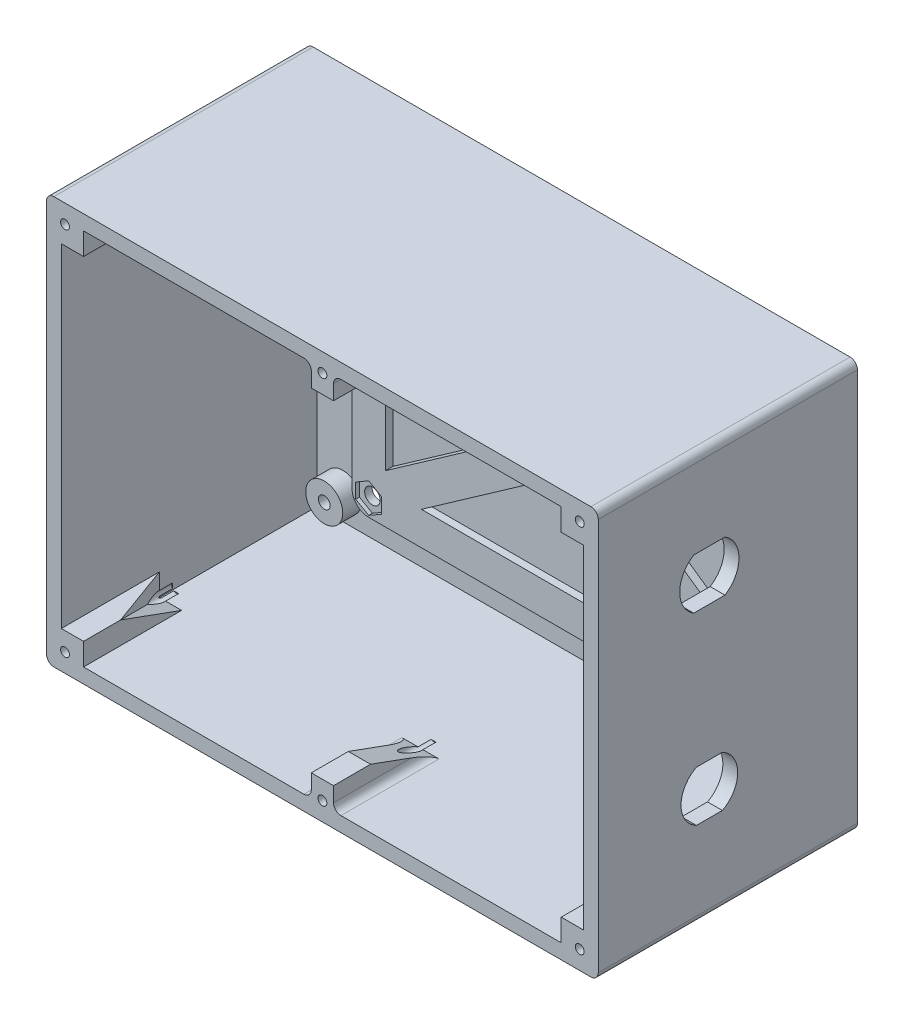
SolidWorks part; units mm, degrees
ref_plane "Přední rovina" through (0, 0, 0) normal (0, 0, 1) x (1, 0, 0)
ref_plane "Horní rovina" through (0, 0, 0) normal (0, 1, 0) x (1, 0, 0)
ref_plane "Pravá rovina" through (0, 0, 0) normal (1, 0, 0) x (0, 0, -1)
sketch "Skica1" plane through (0, 0, 0) normal (0, 0, 1) x (1, 0, 0)
  line L1 (-50, -50) -> (50, -50) construction
  line L2 (-50, -50) -> (-50, 50) construction
  line L3 (-50, 50) -> (50, 50) construction
  line L4 (50, -50) -> (50, 50) construction
  line L5 (-50, -50) -> (50, 50) construction
  line L6 (-50, 50) -> (50, -50) construction
  line L7 (-51, -51) -> (90, -51)
  line L8 (-51, -51) -> (-51, 51)
  line L9 (-51, 51) -> (90, 51)
  line L10 (90, -51) -> (90, 51)
  line L11 (-55, -55) -> (94, -55)
  line L12 (-55, -55) -> (-55, 55)
  line L13 (-55, 55) -> (94, 55)
  line L14 (94, -55) -> (94, 55)
  point P0 (0, 0)
  dimension "D1" = 100
  dimension "D2" = 2
  dimension "D3" = 2
  dimension "D4" = 2
  dimension "D5" = 40
  dimension "D6" = 4
  dimension "D7" = 4
  dimension "D8" = 4
  dimension "D9" = 4
extrude "Přidat vysunutím1" add sketch "Skica1" along normal blind 70
extrude "Přidat vysunutím2" add sketch "Skica1<3>" along normal blind 1 contours L7 L10 L9 L8 region at (19.5, 0, 0)
sketch "Skica1<3>" plane through (0, 0, 0) normal (0, 0, 1) x (1, 0, 0) same geometry as "Skica1"
sketch "Skica2" plane through (0, 0, 1) normal (0, 0, 1) x (1, 0, 0)
  line L0 (90, 51) -> (-51, 51) construction
  line L1 (-49, -49) -> (49, -49) construction
  line L2 (-49, -49) -> (-49, 49) construction
  line L3 (-49, 49) -> (49, 49) construction
  line L20 (49, -49) -> (49, 49) construction
  line L21 (-49, -49) -> (49, 49) construction
  line L22 (-49, 49) -> (49, -49) construction
  line L24 (-44, -44) -> (44, -44) construction
  line L25 (-44, -44) -> (-44, 44) construction
  line L26 (-44, 44) -> (44, 44) construction
  line L27 (44, -44) -> (44, 44) construction
  line L28 (-44, -44) -> (44, 44) construction
  line L29 (-44, 44) -> (44, -44) construction
  circle A0 centre (-44, 44) radius 1.6
  circle A1 centre (44, 44) radius 1.6
  circle A2 centre (44, -44) radius 1.6
  circle A3 centre (-44, -44) radius 1.6
  circle A4 centre (-44, 44) radius 5
  circle A5 centre (44, 44) radius 5
  circle A6 centre (44, -44) radius 5
  circle A7 centre (-44, -44) radius 5
  point P0 (0, 0)
  point P7 (0, 0)
  dimension "D3" = 3.2
  dimension "D1" = 2
  dimension "D2" = 5
extrude "Přidat vysunutím3" add sketch "Skica2" along normal blind 5
extrude "Odebrat vysunutím1" cut sketch "Skica2<2>" against normal through all both and the other way through all contours A0 | A1 | A2 | A3 region at (-44, 44, 1) region at (44, 44, 1) region at (44, -44, 1) region at (-44, -44, 1)
sketch "Skica2<2>" plane through (0, 0, 1) normal (0, 0, 1) x (1, 0, 0) same geometry as "Skica2"
sketch "Skica6" plane through (94, 0, 0) normal (1, 0, 0) x (0, 0, -1)
  line L0 (-40, -55) -> (-40, 55) construction
  line L1 (-70, -55) -> (0, -55) construction
  line L2 (-70, 55) -> (0, 55) construction
  line L3 (-44.2143, 31.8) -> (-35.7857, 31.8)
  line L4 (-44.2143, 18.2) -> (-35.7857, 18.2)
  line L6 (0, -55) -> (0, 55) construction
  line L7 (-43.5046, -18.2) -> (-36.4954, -18.2)
  line L8 (-43.5046, -31.8) -> (-36.4954, -31.8)
  arc A0 (-43.5046, -18.2) -> (-43.5046, -31.8) centre (-40, -25) ccw
  arc A1 (-44.2143, 31.8) -> (-44.2143, 18.2) centre (-40, 25) ccw
  arc A2 (-35.7857, 18.2) -> (-35.7857, 31.8) centre (-40, 25) ccw
  arc A3 (-36.4954, -31.8) -> (-36.4954, -18.2) centre (-40, -25) ccw
  dimension "D1" = 15.3
  dimension "D2" = 16
  dimension "D3" = 13.6
  dimension "D4" = 30
  dimension "D5" = 30
  dimension "D6" = 40
  dimension "D7" = 13.6
extrude "Odebrat vysunutím2" cut sketch "Skica6" against normal up to surface (4 mm away) up to face at (90, 0, 35.5)
sketch "Skica7" plane through (0, 0, 1) normal (0, 0, 1) x (1, 0, 0)
  line L0 (94, 55) -> (-55, 55) construction
  line L1 (-35, -40) -> (79, -40) construction
  line L2 (-35, -40) -> (-35, -37.9) construction
  line L3 (-35, 40) -> (-32.9, 40) construction
  line L4 (79, -40) -> (79, 35.5) construction
  line L5 (-55, -55) -> (94, -55) construction
  line L6 (-55, 55) -> (-55, -55) construction
  line L7 (94, -55) -> (94, 55) construction
  line L8 (76.9, 40) -> (79, 40) construction
  line L9 (74.5, -31.3446) -> (29.8339, 0)
  line L10 (64.7536, 35.5) -> (22, 5.4975)
  line L11 (-20.7536, -35.5) -> (22, -5.4975)
  line L12 (-39.5, 40) -> (-39.5, -40)
  line L13 (-30.5, -31.3446) -> (-30.5, 31.3446)
  line L14 (-35, -44.5) -> (39.0251, -44.5)
  line L15 (64.7536, -35.5) -> (-20.7536, -35.5)
  line L16 (83.5, -40) -> (83.5, 40)
  line L17 (22, -5.4975) -> (64.7536, -35.5)
  line L18 (22, 5.4975) -> (-20.7536, 35.5)
  line L19 (39.0251, 44.5) -> (-35, 44.5)
  line L20 (79, 44.5) -> (48.9749, 44.5)
  line L21 (74.5, 31.3446) -> (74.5, -31.3446)
  line L22 (29.8339, 0) -> (74.5, 31.3446)
  line L23 (14.1661, 0) -> (-30.5, -31.3446)
  line L24 (-30.5, 31.3446) -> (14.1661, 0)
  line L25 (48.9749, -44.5) -> (79, -44.5)
  line L26 (-35, -35.5) -> (-35, 35.5) construction
  line L27 (79, 37.9) -> (79, 40) construction
  line L28 (-20.7536, 35.5) -> (64.7536, 35.5)
  line L30 (71.1661, 40) -> (74.5, 40) construction
  line L31 (-35, 37.9) -> (-35, 40) construction
  circle A0 centre (-35, 40) radius 2.1
  arc A1 (-35, 44.5) -> (-39.5, 40) centre (-35, 40) ccw
  circle A2 centre (79, 40) radius 2.1
  arc A3 (83.5, 40) -> (79, 44.5) centre (79, 40) ccw
  circle A4 centre (79, -40) radius 2.1
  arc A5 (79, -44.5) -> (83.5, -40) centre (79, -40) ccw
  circle A6 centre (-35, -40) radius 2.1
  arc A7 (-39.5, -40) -> (-35, -44.5) centre (-35, -40) ccw
  circle A8 centre (44, 44) radius 5 construction
  circle A9 centre (44, -44) radius 5 construction
  arc A10 (39.0251, 44.5) -> (48.9749, 44.5) centre (44, 44) ccw
  arc A11 (48.9749, -44.5) -> (39.0251, -44.5) centre (44, -44) ccw
  dimension "D5" = 4.2
  dimension "D6" = 9
  dimension "D1" = 15
  dimension "D2" = 15
  dimension "D3" = 20
  dimension "D4" = 15
extrude "Přidat vysunutím4" add sketch "Skica7" along normal blind 2
extrude "Odebrat vysunutím3" cut sketch "Skica7<2>" against normal through all contours A0 | A2 | A4 | A6 region at (-35, 40, 1) region at (79, 40, 1) region at (79, -40, 1) region at (-35, -40, 1)
sketch "Skica7<2>" plane through (0, 0, 1) normal (0, 0, 1) x (1, 0, 0) same geometry as "Skica7"
sketch "Skica8" plane through (0, 0, 3) normal (0, 0, 1) x (1, 0, 0)
  line L1 (-35, 35.9585) -> (-31.5, 37.9793)
  line L2 (-31.5, 37.9793) -> (-31.5, 42.0207)
  line L3 (-31.5, 42.0207) -> (-35, 44.0415)
  line L4 (-35, 44.0415) -> (-38.5, 42.0207)
  line L5 (-38.5, 42.0207) -> (-38.5, 37.9793)
  line L6 (-38.5, 37.9793) -> (-35, 35.9585)
  line L7 (-35, -35.9585) -> (-38.5, -37.9793)
  line L8 (-38.5, -37.9793) -> (-38.5, -42.0207)
  line L9 (-38.5, -42.0207) -> (-35, -44.0415)
  line L10 (-35, -44.0415) -> (-31.5, -42.0207)
  line L11 (-31.5, -42.0207) -> (-31.5, -37.9793)
  line L12 (-31.5, -37.9793) -> (-35, -35.9585)
  line L13 (79, -35.9585) -> (75.5, -37.9793)
  line L14 (75.5, -37.9793) -> (75.5, -42.0207)
  line L15 (75.5, -42.0207) -> (79, -44.0415)
  line L16 (79, -44.0415) -> (82.5, -42.0207)
  line L17 (82.5, -42.0207) -> (82.5, -37.9793)
  line L18 (82.5, -37.9793) -> (79, -35.9585)
  line L19 (79, 35.9585) -> (82.5, 37.9793)
  line L20 (82.5, 37.9793) -> (82.5, 42.0207)
  line L21 (82.5, 42.0207) -> (79, 44.0415)
  line L22 (79, 44.0415) -> (75.5, 42.0207)
  line L23 (75.5, 42.0207) -> (75.5, 37.9793)
  line L24 (75.5, 37.9793) -> (79, 35.9585)
  circle A4 centre (-35, 40) radius 3.5 construction
  circle A5 centre (-35, -40) radius 3.5 construction
  circle A6 centre (79, -40) radius 3.5 construction
  circle A7 centre (79, 40) radius 3.5 construction
  dimension "D1" = 7
extrude "Odebrat vysunutím4" cut sketch "Skica8" against normal blind 1
sketch "Skica9" plane through (0, 0, 0) normal (0, 0, -1) x (-1, 0, 0)
  line L1 (-44, 40.8246) -> (-41.25, 42.4123)
  line L2 (-41.25, 42.4123) -> (-41.25, 45.5877)
  line L3 (-41.25, 45.5877) -> (-44, 47.1754)
  line L4 (-44, 47.1754) -> (-46.75, 45.5877)
  line L5 (-46.75, 45.5877) -> (-46.75, 42.4123)
  line L6 (-46.75, 42.4123) -> (-44, 40.8246)
  line L19 (-44, -47.1754) -> (-41.25, -45.5877)
  line L20 (-41.25, -45.5877) -> (-41.25, -42.4123)
  line L21 (-41.25, -42.4123) -> (-44, -40.8246)
  line L22 (-44, -40.8246) -> (-46.75, -42.4123)
  line L23 (-46.75, -42.4123) -> (-46.75, -45.5877)
  line L24 (-46.75, -45.5877) -> (-44, -47.1754)
  line L25 (44, -47.1754) -> (46.75, -45.5877)
  line L26 (46.75, -45.5877) -> (46.75, -42.4123)
  line L27 (46.75, -42.4123) -> (44, -40.8246)
  line L28 (44, -40.8246) -> (41.25, -42.4123)
  line L29 (41.25, -42.4123) -> (41.25, -45.5877)
  line L30 (41.25, -45.5877) -> (44, -47.1754)
  line L31 (44, 40.8246) -> (46.75, 42.4123)
  line L32 (46.75, 42.4123) -> (46.75, 45.5877)
  line L33 (46.75, 45.5877) -> (44, 47.1754)
  line L34 (44, 47.1754) -> (41.25, 45.5877)
  line L35 (41.25, 45.5877) -> (41.25, 42.4123)
  line L36 (41.25, 42.4123) -> (44, 40.8246)
  circle A0 centre (-44, 44) radius 2.75 construction
  circle A3 centre (-44, -44) radius 2.75 construction
  circle A4 centre (44, -44) radius 2.75 construction
  circle A5 centre (44, 44) radius 2.75 construction
  dimension "D1" = 5.5
extrude "Odebrat vysunutím5" cut sketch "Skica9" against normal blind 2.5
sketch "Skica10" plane through (0, 0, 70) normal (0, 0, 1) x (1, 0, 0)
  line L0 (90, 51) -> (-51, 51) construction
  line L1 (-51, 51) -> (-45, 51)
  line L2 (-51, 51) -> (-51, 45)
  line L3 (-51, 45) -> (-45, 45)
  line L4 (-45, 51) -> (-45, 45)
  line L5 (90, 51) -> (84, 51)
  line L6 (90, 51) -> (90, 45)
  line L7 (90, 45) -> (84, 45)
  line L8 (84, 51) -> (84, 45)
  line L9 (90, -51) -> (84, -51)
  line L10 (90, -51) -> (90, -45)
  line L11 (90, -45) -> (84, -45)
  line L12 (84, -51) -> (84, -45)
  line L13 (-51, -51) -> (-45, -51)
  line L14 (-51, -51) -> (-51, -45)
  line L15 (-51, -45) -> (-45, -45)
  line L16 (-45, -51) -> (-45, -45)
  line L17 (16.5, 51) -> (22.5, 51)
  line L18 (16.5, 51) -> (16.5, 45)
  line L19 (16.5, 45) -> (22.5, 45)
  line L20 (22.5, 51) -> (22.5, 45)
  line L21 (-51, -51) -> (90, -51) construction
  line L22 (22.5, -51) -> (16.5, -51)
  line L23 (22.5, -51) -> (22.5, -45)
  line L24 (22.5, -45) -> (16.5, -45)
  line L25 (16.5, -51) -> (16.5, -45)
  line L27 (-55, 55) -> (-55, -55) construction
  point P32 (19.5, -51)
  point P34 (19.5, 45)
  dimension "D1" = 74.5
  dimension "D2" = 74.5
  dimension "D3" = 6
extrude "Přidat vysunutím5" add sketch "Skica10" against normal blind 10
chamfer "Zkosení1" distance 6 angle 70 10 edges at (-51, 48, 60) (-48, 51, 60) (-48, -51, 60) (-51, -48, 60) (19.5, 51, 60) (19.5, -51, 60) (90, -48, 60) (87, -51, 60) (87, 51, 60) (90, 48, 60) first distance on face at (-48, 48, 60) first distance on face at (-48, -48, 60) first distance on face at (19.5, 48, 60) first distance on face at (19.5, -48, 60) first distance on face at (87, -48, 60) first distance on face at (87, 48, 60)
sketch "Skica11" plane through (0, 0, 70) normal (0, 0, 1) x (1, 0, 0)
  line L1 (-50, -50) -> (89, -50) construction
  line L2 (-50, -50) -> (-50, 50) construction
  line L3 (-50, 50) -> (89, 50) construction
  line L4 (89, -50) -> (89, 50) construction
  line L6 (84, 45) -> (94, 55) construction
  line L7 (-45, -45) -> (-55, -55) construction
  circle A0 centre (-50, 50) radius 1.2
  circle A1 centre (19.5, 50) radius 1.2
  circle A2 centre (89, 50) radius 1.2
  circle A3 centre (89, -50) radius 1.2
  circle A4 centre (19.5, -50) radius 1.2
  circle A5 centre (-50, -50) radius 1.2
  dimension "D1" = 2.4
extrude "Odebrat vysunutím6" cut sketch "Skica11" against normal blind 30
fillet "Zaoblit1" radius 2 4 edges at (94, -55, 35) (-55, -55, 35) (94, 55, 35) (-55, 55, 35)
fillet "Zaoblit2" radius 2 4 edges at (16.5, -51, 56.7576) (22.5, -51, 56.7576) (22.5, 51, 56.7576) (16.5, 51, 56.7576)
